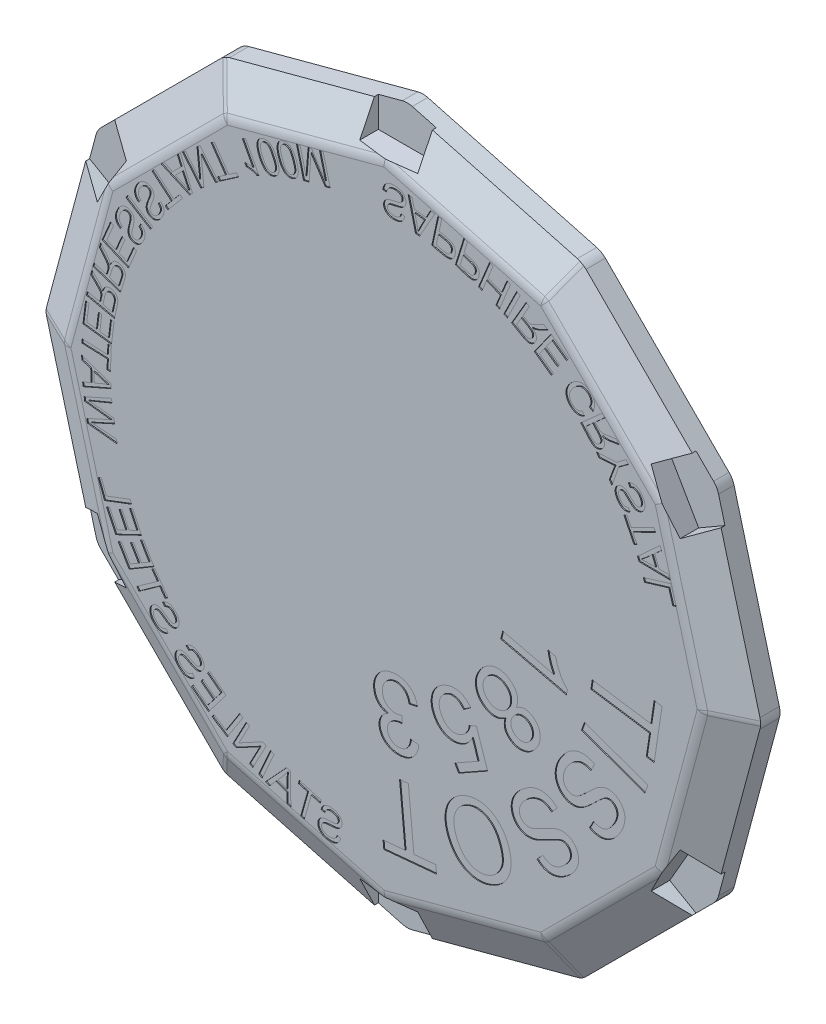
SolidWorks part; units mm, degrees
ref_plane "Front Plane" through (0, 0, 0) normal (0, 0, 1) x (1, 0, 0)
ref_plane "Top Plane" through (0, 0, 0) normal (0, 1, 0) x (1, 0, 0)
ref_plane "Right Plane" through (0, 0, 0) normal (1, 0, 0) x (0, 0, -1)
sketch "Sketch1" plane through (0, 0, 0) normal (0, 0, 1) x (1, 0, 0)
  line L0 (0, 18.5) -> (-9.25, 16.0215)
  line L1 (-9.25, 16.0215) -> (-16.0215, 9.25)
  line L2 (-16.0215, 9.25) -> (-18.5, 0)
  line L3 (-18.5, 0) -> (-16.0215, -9.25)
  line L4 (-16.0215, -9.25) -> (-9.25, -16.0215)
  line L5 (-9.25, -16.0215) -> (0, -18.5)
  line L6 (0, -18.5) -> (9.25, -16.0215)
  line L7 (9.25, -16.0215) -> (16.0215, -9.25)
  line L8 (16.0215, -9.25) -> (18.5, 0)
  line L9 (18.5, 0) -> (16.0215, 9.25)
  line L10 (16.0215, 9.25) -> (9.25, 16.0215)
  line L11 (9.25, 16.0215) -> (0, 18.5)
  circle A0 centre (0, 0) radius 17.8696 construction
extrude "Boss-Extrude1" add sketch "Sketch1" along normal blind 2
chamfer "Chamfer1" distance 1 distance2 2 12 edges at (12.6357, 12.6357, 2) (17.2607, 4.625, 2) (17.2607, -4.625, 2) (12.6357, -12.6357, 2) (4.625, -17.2607, 2) (-4.625, -17.2607, 2) (-12.6357, -12.6357, 2) (-17.2607, -4.625, 2) (-17.2607, 4.625, 2) (-12.6357, 12.6357, 2) (-4.625, 17.2607, 2) (4.625, 17.2607, 2) first distance on face at (12.6357, 12.6357, 1) first distance on face at (17.2607, 4.625, 1) first distance on face at (17.2607, -4.625, 1) first distance on face at (12.6357, -12.6357, 1) first distance on face at (4.625, -17.2607, 1) first distance on face at (-4.625, -17.2607, 1) first distance on face at (-12.6357, -12.6357, 1) first distance on face at (-17.2607, -4.625, 1) first distance on face at (-17.2607, 4.625, 1) first distance on face at (-12.6357, 12.6357, 1) first distance on face at (-4.625, 17.2607, 1) first distance on face at (4.625, 17.2607, 1)
sketch "Sketch2" [suppressed] plane through (0, 0, 2) normal (0, 0, 1) x (1, 0, 0)
  circle A0 centre (0, 0) radius 0.05
  dimension "D1" = 0.1
extrude "Cut-Extrude1" [suppressed] cut sketch "Sketch2" against normal blind 1
sketch "Sketch3" plane through (0, 0, 2) normal (0, 0, 1) x (1, 0, 0)
  line L0 (-1.4976, 18.8882) -> (-1.4976, 16.5277)
  line L1 (-1.4976, 16.5277) -> (1.4976, 16.5277)
  line L2 (1.4976, 16.5277) -> (1.4976, 19.1569)
  line L3 (1.4976, 19.1569) -> (-1.4976, 19.1569)
  line L4 (-1.4976, 19.1569) -> (-1.4976, 18.8882)
  line L6 (0, 16.4294) -> (0, 20.0975) construction
  dimension "D1" = 2.9953
extrude "Cut-Extrude2" cut sketch "Sketch3" against normal blind 1.2
pattern_circular "CirPattern1" count 6 over 360 of "Cut-Extrude2"
fillet "Fillet1" radius 1 18 edges at (0, -18.5, 0.4) (-16.0215, -9.25, 0.4) (-17.4647, 0, 1.5) (-18.5, 0, 0.5) (-16.0215, 9.25, 0.4) (-8.7324, 15.1249, 1.5) (-9.25, 16.0215, 0.5) (0, 18.5, 0.4) (8.7324, 15.1249, 1.5) (9.25, 16.0215, 0.5) (16.0215, 9.25, 0.4) (18.5, 0, 0.5) (17.4647, 0, 1.5) (16.0215, -9.25, 0.4) (9.25, -16.0215, 0.5) (8.7324, -15.1249, 1.5) (-9.25, -16.0215, 0.5) (-8.7324, -15.1249, 1.5)
fillet "Fillet2" radius 1 18 edges at (-11.2639, 11.1792, 2) (-8.2069, 14.2148, 2) (-4.0495, 15.3444, 2) (4.0495, 15.3444, 2) (8.2069, 14.2148, 2) (11.2639, 11.1792, 2) (15.3134, 4.1652, 2) (16.4139, 0, 2) (15.3134, -4.1652, 2) (11.2639, -11.1792, 2) (8.2069, -14.2148, 2) (4.0495, -15.3444, 2) (-4.0495, -15.3444, 2) (-8.2069, -14.2148, 2) (-11.2639, -11.1792, 2) (-15.3134, -4.1652, 2) (-16.4139, 0, 2) (-15.3134, 4.1652, 2)
sketch "Sketch4" plane through (0, 0, 2) normal (0, 0, 1) x (1, 0, 0)
  circle A0 centre (0, 0) radius 15.6336 construction
  text T0 "               STAINLES STEEL   WATERRESISTANT 100M     SAPPHIRE CRYSTAL       " font "Arial" height 1.5
extrude "Cut-Extrude3" cut sketch "Sketch4" against normal blind 0.05
sketch "Sketch7" plane through (0, 0, 2) normal (0, 0, 1) x (1, 0, 0)
  circle A0 centre (0, 0) radius 10.9492 construction
  text T0 "             TISSOT                                      " font "Arial" height 3.5
extrude "Cut-Extrude5" cut sketch "Sketch7" against normal blind 0.05
sketch "Sketch8" plane through (0, 0, 2) normal (0, 0, 1) x (1, 0, 0)
  circle A0 centre (0, 0) radius 6.4543 construction
  text T0 "             1853                      " font "Arial" height 3.5
extrude "Cut-Extrude6" cut sketch "Sketch8" against normal blind 0.05
sketch "Sketch9" plane through (0, 0, 2) normal (0, 0, 1) x (1, 0, 0)
  circle A0 centre (0, 0) radius 6.2329 construction
